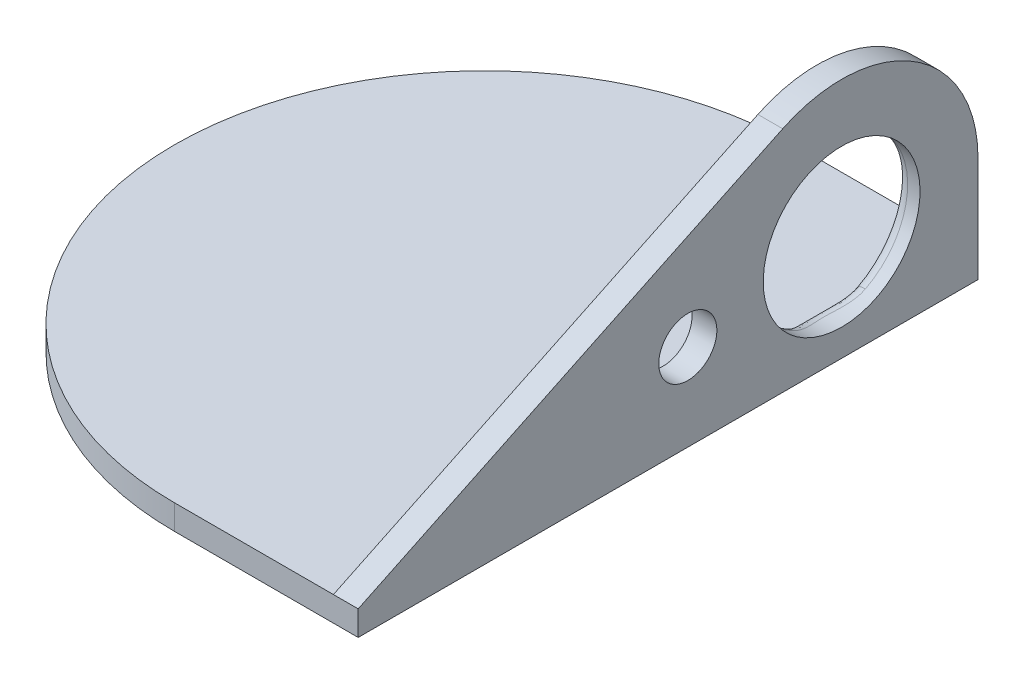
SolidWorks part; units mm, degrees
ref_plane "Front Plane" through (0, 0, 0) normal (0, 0, 1) x (1, 0, 0)
ref_plane "Top Plane" through (0, 0, 0) normal (0, 1, 0) x (1, 0, 0)
ref_plane "Right Plane" through (0, 0, 0) normal (1, 0, 0) x (0, 0, -1)
sketch "Sketch2" plane through (0, 0, 0) normal (0, 0, 1) x (1, 0, 0)
  line L0 (0, 8.1269) -> (0, -11.1542) construction
  line L1 (-11.5687, 0) -> (13.6229, 0) construction
  line L2 (0, 0) -> (-25.4, 0)
  line L3 (0, 0) -> (0, 25.4)
  dimension "D1" = 25.4
  dimension "D2" = 25.4
extrude "Extrude-Thin1" add sketch "Sketch2" along normal mid plane 25.4 thin thin type one direction wall 1.016
sketch "Sketch3" plane through (0, 0, 0) normal (-1, 0, 0) x (0, 0, 1)
  line L0 (12.7, 0) -> (-12.7, 0) construction
  line L5 (-12.7, 0) -> (-12.7, 25.4) construction
  line L6 (-7.112, 24.7498) -> (-7.112, -12.364) construction
  line L7 (-20.3076, 3.302) -> (17.3462, 3.302) construction
  circle A0 centre (-7.112, 3.302) radius 3.2131
  dimension "D2" = 6.4262
  dimension "D1" = 3.302
  dimension "D3" = 5.588
extrude "Cut-Extrude1" cut sketch "Sketch3" against normal through all
sketch "Sketch4" plane through (0, 0, 0) normal (-1, 0, 0) x (0, 0, 1)
  line L0 (-12.7, 0) -> (-12.7, 25.4) construction
  line L1 (12.7, 0) -> (-4.6961, 8.3408)
  line L5 (-12.7, 3.302) -> (-12.7, 25.4)
  line L6 (-12.7, 25.4) -> (12.7, 25.4)
  line L7 (12.7, 25.4) -> (12.7, 0)
  line L8 (12.7, 0) -> (-12.7, 0) construction
  arc A0 (-4.6961, 8.3408) -> (-12.7, 3.302) centre (-7.112, 3.302) ccw
  circle A1 centre (-0.8079, 2.54) radius 1.1906
  dimension "D1" = 2.3813
  dimension "D2" = 6.35
  dimension "D3" = 2.54
extrude "Cut-Extrude3" cut sketch "Sketch4" against normal through all
sketch "Sketch6" plane through (0, 0, 0) normal (0, 1, 0) x (1, 0, 0)
  line L0 (0, 12.7) -> (-11.43, 12.7)
  line L2 (-11.43, 12.7) -> (-25.4, 0)
  line L3 (-25.4, -12.7) -> (-25.4, 12.7) construction
  line L4 (-25.4, 0) -> (-11.43, -12.7)
  line L6 (-11.43, -12.7) -> (0, -12.7)
  line L7 (-25.4, 12.7) -> (0, 12.7) construction
  line L8 (-25.4, -12.7) -> (0, -12.7) construction
  point P3 (-12.7, 12.7)
  point P4 (-13.3611, 12.7)
  point P5 (-12.7, 12.7)
  point P10 (-10.2992, -12.7)
  point P16 (0, 0)
  point P18 (-11.43, -12.7)
  point P19 (-25.4, 0)
  line M4 (0, 12.7) -> (-25.4, 12.7)
  line M5 (-25.4, 12.7) -> (-25.4, -12.7)
  line M6 (-25.4, -12.7) -> (0, -12.7)
  dimension "D1" = 11.43
extrude "Cut-Extrude4" cut sketch "Sketch6" against normal through all both and the other way through all contours L2 M4 M5 | L4 M5 M6
fillet "Fillet2" radius 12.7 3 edges at (-11.43, -0.508, 12.7) (-11.43, -0.508, -12.7) (-25.4, -0.508, 0)
fillet "Fillet3" radius 0.508 1 edges at (0, 0.0889, -7.112)
